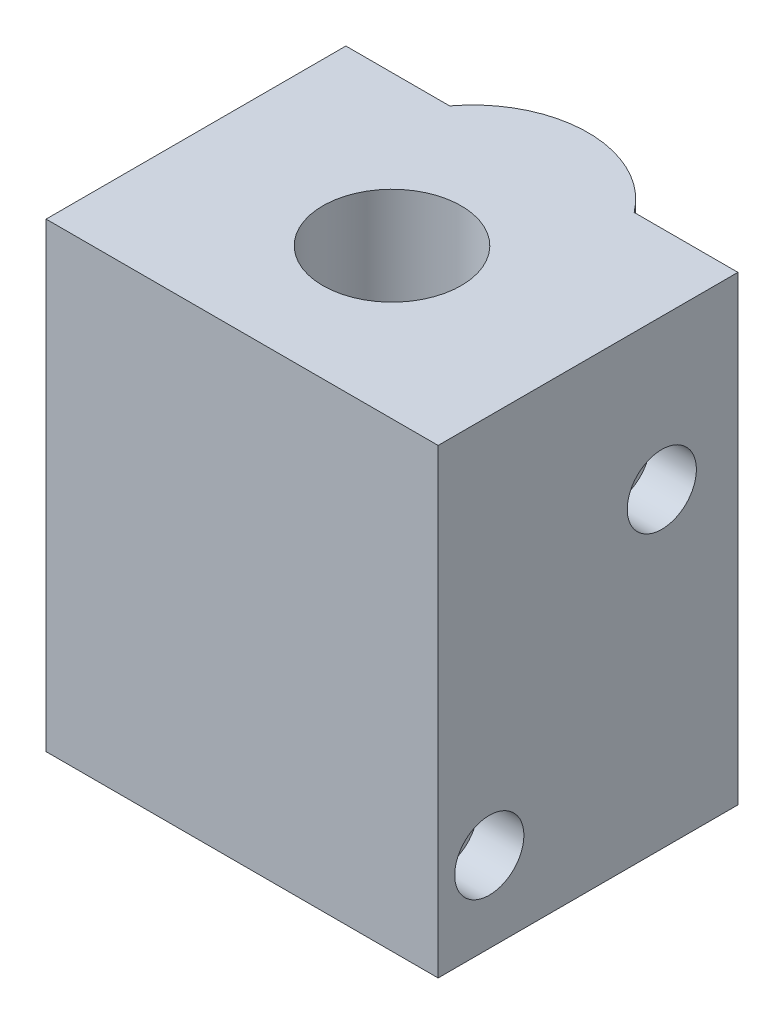
SolidWorks part; units mm, degrees
ref_plane "Front Plane" through (0, 0, 0) normal (0, 0, 1) x (1, 0, 0)
ref_plane "Top Plane" through (0, 0, 0) normal (0, 1, 0) x (1, 0, 0)
ref_plane "Right Plane" through (0, 0, 0) normal (1, 0, 0) x (0, 0, -1)
sketch "Sketch1" plane through (0, 0, 0) normal (0, 1, 0) x (1, 0, 0)
  line L0 (8.5, 0) -> (8.5, 10) construction
  line L1 (0, 0) -> (17, 0)
  line L2 (0, 0) -> (0, 13)
  line L3 (0, 13) -> (4.5, 13)
  line L4 (17, 0) -> (17, 13)
  line L5 (12.5, 13) -> (17, 13)
  arc A0 (4.5, 13) -> (12.5, 13) centre (8.5, 10) cw
  point P8 (8.5, 15)
  dimension "D1" = 17
  dimension "D2" = 13
  dimension "D3" = 15
  dimension "D4" = 8
extrude "Boss-Extrude1" add sketch "Sketch1" along normal blind 20
sketch "Sketch2" plane through (0, 20, 0) normal (0, 1, 0) x (1, 0, 0)
  line L0 (0, 6.5) -> (8.5, 6.5) construction
  line L1 (0, 13) -> (0, 0) construction
  line L2 (8.5, 0) -> (8.5, 6.5) construction
  line L3 (0, 0) -> (17, 0) construction
  circle A0 centre (8.5, 6.5) radius 3
  dimension "D1" = 6
extrude "Cut-Extrude1" cut sketch "Sketch2" against normal offset from surface (12 mm away) 12 up to face at (8.5, 20, -9)
sketch "Sketch3" plane through (0, 8, 0) normal (0, 1, 0) x (1, 0, 0)
  circle A0 centre (8.5, 6.5) radius 1.75
  circle A1 centre (8.5, 6.5) radius 3 construction
  dimension "D1" = 3.5
extrude "Cut-Extrude2" cut sketch "Sketch3" against normal through all
sketch "Sketch4" plane through (17, 0, 0) normal (1, 0, 0) x (0, 0, -1)
  line L0 (13, 20) -> (13, 0) construction
  line L1 (0, 20) -> (13, 20) construction
  circle A0 centre (9.7, 13.5) radius 1.5
  circle A1 centre (2.2192, 3.5) radius 1.5
  point P4 (2.2192, 2.7609)
  point P5 (10.6763, 17.434)
  point P8 (0, 0)
  point P10 (9.829, 19.1897)
  dimension "D1" = 3
  dimension "D2" = 3.3
  dimension "D3" = 6.5
  dimension "D4" = 16.5
extrude "Cut-Extrude3" cut sketch "Sketch4" against normal blind 2
